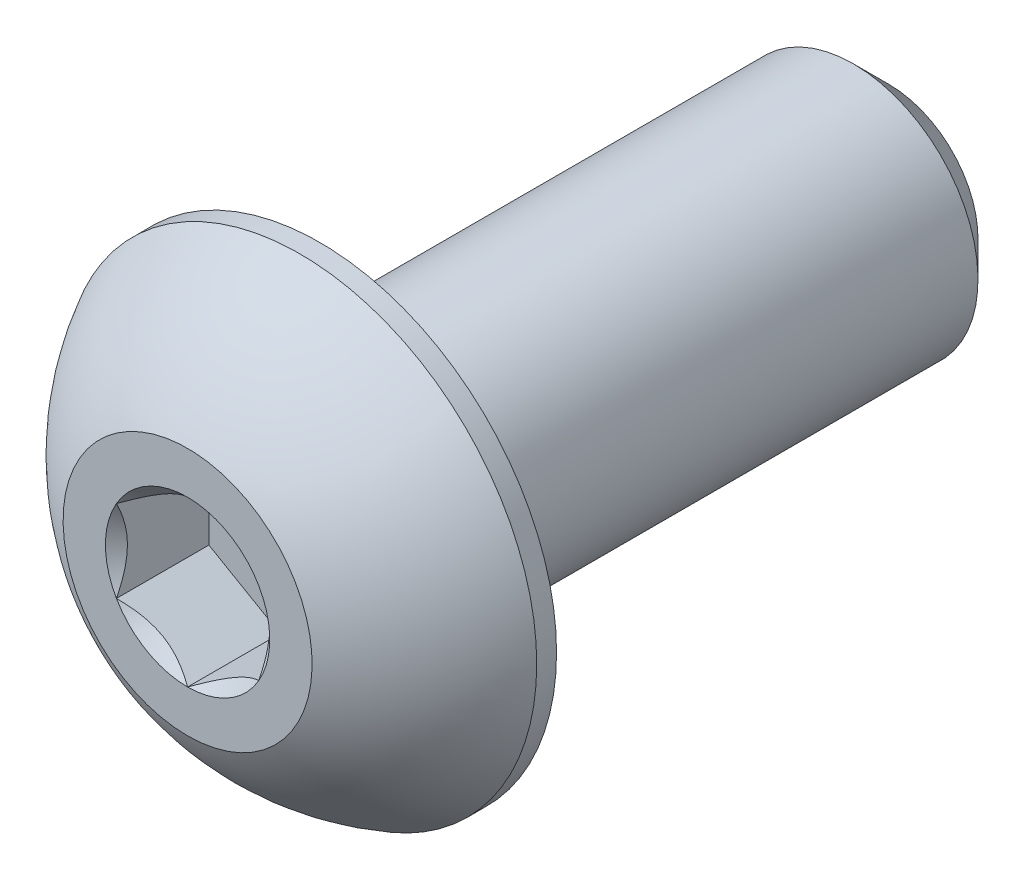
SolidWorks part; units mm, degrees
material "AISI 304"
ref_plane "Front" through (0, 0, 0) normal (0, 0, 1) x (1, 0, 0)
ref_plane "Top" through (0, 0, 0) normal (0, 1, 0) x (1, 0, 0)
ref_plane "Right" through (0, 0, 0) normal (1, 0, 0) x (0, 0, -1)
sketch "Sketch1" plane through (0, 0, 0) normal (1, 0, 0) x (0, 0, -1)
  line L2 (2.2098, 2.0828) -> (11.7348, 2.0828)
  line L3 (11.7348, 2.0828) -> (11.7348, 0)
  line L4 (11.7348, 0) -> (2.2098, 0)
  line L6 (1.8783, 3.9624) -> (2.2098, 3.9624) construction
  line L7 (11.7348, 2.0828) -> (11.7348, -2.0828) construction
  line L8 (0, 0) -> (2.2098, 0) construction
  line L9 (2.2098, 3.9624) -> (2.2098, -3.9624) construction
  line L11 (2.2098, 2.0828) -> (2.2098, 0)
  line L13 (0, 1.1906) -> (0, -1.1906) construction
  line L14 (0, 1.1906) -> (0, 2.0828) construction
  arc A3 (0, 2.0828) -> (1.8783, 3.9624) centre (3.9638, 0) cw construction
  dimension "D1" = 0.3315
revolve "Revolve1" add sketch "Sketch1" angle 360 mid plane about L4
sketch "Sketch3" plane through (0, 0, -11.7348) normal (0, 0, -1) x (-1, 0, 0)
  circle A0 centre (0, 0) radius 2.0828
curve "Helix/Spiral1" pitch 0.7937 height 10.3188 turns 13
sketch "Sketch2" plane through (0, 0, 0) normal (1, 0, 0) x (0, 0, -1)
  line L0 (11.7348, 2.0828) -> (12.4293, 2.0828)
  line L1 (12.4293, 2.0828) -> (12.1317, 1.5672)
  line L2 (12.1317, 1.5672) -> (12.0325, 1.5672)
  line L3 (12.0325, 1.5672) -> (11.7348, 2.0828)
  line L4 (11.8836, 1.825) -> (12.2805, 1.825) construction
  dimension "D1" = 60
  dimension "D2" = 0.0992
  dimension "D3" = 0.3969
chamfer "Chamfer1" distance 0.5953 angle 45 1 edges at (0, 2.0828, -11.7348)
sweep "Cut-Sweep1" [suppressed] cut profiles "Sketch2" path "Helix/Spiral1"
sketch "Sketch7" plane through (0, 0, 0) normal (1, 0, 0) x (0, 0, -1)
  line L6 (1.8783, 3.9624) -> (2.2098, 3.9624) construction
  line L8 (0, 0) -> (2.2098, 0) construction
  line L11 (2.2098, 3.9624) -> (2.2098, -3.9624) construction
  line L12 (1.8783, 3.9624) -> (2.2098, 3.9624)
  line L13 (0, 0) -> (2.2098, 0)
  line L14 (0, 1.1906) -> (0, -1.1906) construction
  line L15 (2.2098, 3.9624) -> (2.2098, 0)
  line L16 (0, 2.0828) -> (0, 0)
  arc A2 (1.8783, 3.9624) -> (0, 2.0828) centre (3.9638, 0) ccw construction
  arc A3 (1.8783, 3.9624) -> (0, 2.0828) centre (3.9638, 0) ccw
revolve "Revolve2" add sketch "Sketch7" angle 360 mid plane about L13
sketch "Sketch5" plane through (0, 0, 0) normal (0, 0, 1) x (1, 0, 0)
  line L1 (1.1906, -0.6874) -> (1.1906, 0.6874)
  line L2 (1.1906, 0.6874) -> (0, 1.3748)
  line L3 (0, 1.3748) -> (-1.1906, 0.6874)
  line L4 (-1.1906, 0.6874) -> (-1.1906, -0.6874)
  line L5 (-1.1906, -0.6874) -> (0, -1.3748)
  line L6 (0, -1.3748) -> (1.1906, -0.6874)
  circle A0 centre (0, 0) radius 1.1906 construction
extrude "Cut-Extrude2" cut sketch "Sketch5" against normal blind 1.5469
sketch "Sketch6" plane through (0, 0, 0) normal (0, 0, 1) x (1, 0, 0)
  circle A0 centre (0, 0) radius 1.3748
extrude "Cut-Extrude3" cut sketch "Sketch6" against normal blind 1.5469 draft 45
sketch "Sketch9" [suppressed] plane through (0, 0, -1.4986) normal (0, 0, 1) x (1, 0, 0)
  circle A2 centre (0, 0) radius 1.4224
extrude "Boss-Extrude2" [suppressed] add sketch "Sketch9" against normal offset from surface (12.7 mm away) 31.75
sketch "Sketch10" plane through (0, 0, 0) normal (1, 0, 0) x (0, 0, -1)
  line L0 (11.7348, 2.0828) -> (11.7348, -2.0828) construction
  point P0 (10.5442, -2.0828)
  dimension "D1" = 1.1906
equation "\"D3@Helix/Spiral1\" = \"Lg@Sketch1\" + \"D4@Helix/Spiral1\""
equation "\"D2@Sketch2\" = \"D4@Helix/Spiral1\" * .125"
equation "\"D3@Sketch2\" = \"D4@Helix/Spiral1\" * .5"
equation "\"D1@Chamfer1\" = \"D4@Helix/Spiral1\" * .75"
equation "\"D1@Cut-Extrude2\" = \"Head Ht@Sketch1\" * .7"
equation "\"D1@Sketch1\" = \"Head Ht@Sketch1\" * .15"
equation "\"D1@Sketch10\" = \"D4@Helix/Spiral1\" * 1.5"
equation "\"D1@Cut-Extrude3\" = \"D1@Cut-Extrude2\""
